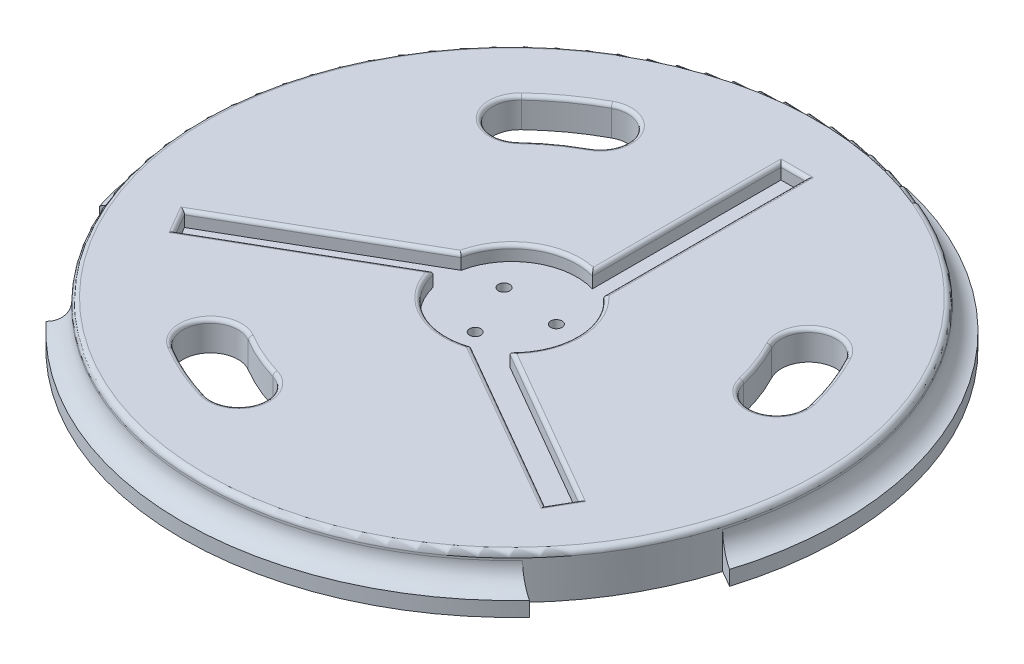
SolidWorks part; units mm, degrees
ref_plane "Alzado" through (0, 0, 0) normal (0, 0, 1) x (1, 0, 0)
ref_plane "Planta" through (0, 0, 0) normal (0, 1, 0) x (1, 0, 0)
ref_plane "Vista lateral" through (0, 0, 0) normal (1, 0, 0) x (0, 0, -1)
sketch "Croquis1" plane through (0, 0, 0) normal (0, 1, 0) x (1, 0, 0)
  line L9 (-64.9347, -24.2163) -> (-2.1479, 12.0337)
  line L10 (-2.1479, 12.0337) -> (1.0271, 6.5345)
  line L11 (1.0271, 6.5345) -> (-61.7597, -29.7155)
  line L12 (-61.7597, -29.7155) -> (-64.9347, -24.2163)
  line L13 (53.3875, -44.1301) -> (-9.3993, -7.8801)
  line L14 (-9.3993, -7.8801) -> (-6.2243, -2.3808)
  line L15 (-6.2243, -2.3808) -> (56.5625, -38.6308)
  line L16 (56.5625, -38.6308) -> (53.3875, -44.1301)
  line L17 (11.524, 68.3) -> (11.524, -4.2)
  line L18 (11.524, -4.2) -> (5.174, -4.2)
  line L19 (5.174, -4.2) -> (5.174, 68.3)
  line L20 (5.174, 68.3) -> (11.524, 68.3)
  line L21 (-7.4511, 5.3057) -> (-0.5604, 9.2841)
  line L22 (-7.4511, 5.3057) -> (-9.0386, 8.0553)
  line L23 (-0.8836, -9.1304) -> (-7.8118, -5.1304)
  line L24 (-0.8836, -9.1304) -> (-2.4711, -11.8801)
  line L25 (8.349, 3.8) -> (8.349, -4.2)
  line L26 (8.349, 3.8) -> (11.524, 3.8)
  arc A0 (11.8909, -12.8396) -> (11.524, 13.17) centre (0, 0) ccw
  arc A1 (-17.0583, -3.9072) -> (5.6435, -16.565) centre (0, 0) ccw
  arc A2 (5.174, 16.7177) -> (-17.1748, 3.3579) centre (0, 0) ccw
  circle A3 centre (-0.8836, -9.1304) radius 1.625
  circle A4 centre (-7.4511, 5.3057) radius 1.625
  circle A5 centre (8.349, 3.8) radius 1.625
sketch "Croquis2" plane through (0, 0, 0) normal (0, 1, 0) x (1, 0, 0)
  line L0 (-64.9347, -24.2163) -> (-2.1479, 12.0337) construction
  line L1 (1.0271, 6.5345) -> (-61.7597, -29.7155) construction
  line L2 (-61.7597, -29.7155) -> (-64.9347, -24.2163) construction
  line L3 (53.3875, -44.1301) -> (-9.3993, -7.8801) construction
  line L4 (-6.2243, -2.3808) -> (56.5625, -38.6308) construction
  line L5 (5.174, -4.2) -> (5.174, 68.3) construction
  line L6 (11.524, 68.3) -> (11.524, -4.2) construction
  line L7 (5.174, 68.3) -> (11.524, 68.3) construction
  line L8 (5.174, 68.3) -> (11.524, 68.3) construction
  line L9 (11.524, 68.3) -> (11.524, 13.17) construction
  line L10 (5.174, 16.7177) -> (5.174, 68.3) construction
  line L11 (11.8909, -12.8396) -> (56.5625, -38.6308) construction
  line L12 (53.3875, -44.1301) -> (5.6435, -16.565) construction
  line L13 (-61.7597, -29.7155) -> (-64.9347, -24.2163) construction
  line L14 (-17.0583, -3.9072) -> (-61.7597, -29.7155) construction
  line L15 (-64.9347, -24.2163) -> (-17.1748, 3.3579) construction
  line L16 (56.5625, -38.6308) -> (53.3875, -44.1301) construction
  line L17 (-65.2762, -24.1248) -> (-17.3979, 3.5178)
  line L18 (-61.8512, -30.057) -> (-65.2762, -24.1248)
  line L19 (-17.2235, -4.2912) -> (-61.8512, -30.057)
  line L20 (53.4791, -44.4716) -> (5.6164, -16.838)
  line L21 (56.9041, -38.5393) -> (53.4791, -44.4716)
  line L22 (12.3066, -12.791) -> (56.9041, -38.5393)
  line L23 (11.774, 68.55) -> (11.774, 13.2829)
  line L24 (4.924, 68.55) -> (11.774, 68.55)
  line L25 (4.924, 17.0534) -> (4.924, 68.55)
  circle A0 centre (0, 0) radius 85
  arc A1 (-17.0583, -3.9072) -> (5.6435, -16.565) centre (0, 0) ccw construction
  arc A2 (11.8909, -12.8396) -> (11.524, 13.17) centre (0, 0) ccw construction
  arc A3 (5.174, 16.7177) -> (-17.1748, 3.3579) centre (0, 0) ccw construction
  arc A4 (5.174, 16.7177) -> (-17.1748, 3.3579) centre (0, 0) ccw construction
  arc A5 (11.8909, -12.8396) -> (11.524, 13.17) centre (0, 0) ccw construction
  arc A6 (-17.0583, -3.9072) -> (5.6435, -16.565) centre (0, 0) ccw construction
  arc A7 (4.924, 17.0534) -> (-17.3979, 3.5178) centre (0, 0) ccw
  arc A8 (-17.2235, -4.2912) -> (5.6164, -16.838) centre (0, 0) ccw
  arc A9 (12.3066, -12.791) -> (11.774, 13.2829) centre (0, 0) ccw
  dimension "D1" = 170
  dimension "D2" = 0.25
extrude "Saliente-Extruir1" add sketch "Croquis2" along normal blind 4
sketch "Croquis3" plane through (0, 0, 0) normal (0, 1, 0) x (1, 0, 0)
  circle A0 centre (0, 0) radius 85
  dimension "D1" = 170
extrude "Saliente-Extruir2" add sketch "Croquis3" against normal blind 4
sketch "Croquis4" plane through (0, 0, 0) normal (0, 1, 0) x (1, 0, 0)
  circle A0 centre (-0.8836, -9.1304) radius 1.625 construction
  circle A1 centre (8.349, 3.8) radius 1.625 construction
  circle A2 centre (-7.4511, 5.3057) radius 1.625 construction
  circle A3 centre (-0.8836, -9.1304) radius 1.625
  circle A4 centre (8.349, 3.8) radius 1.625
  circle A5 centre (-7.4511, 5.3057) radius 1.625
  circle A6 centre (-7.4511, 5.3057) radius 1.625
  circle A7 centre (8.349, 3.8) radius 1.55
  circle A8 centre (-0.8836, -9.1304) radius 1.55
  circle A9 centre (-7.4511, 5.3057) radius 1.55
  dimension "D1" = 3.1
  dimension "D2" = 3.1
  dimension "D3" = 3.1
extrude "Cortar-Extruir2" cut sketch "Croquis4" against normal blind 4 contours A9 | A7 | A8 region at (8.349, 0, -3.8) region at (-0.8836, 0, 9.1304) region at (-7.4511, 0, -5.3057)
sketch "Croquis5" plane through (0, -4, 0) normal (0, -1, 0) x (1, 0, 0)
  circle A0 centre (0, 0) radius 90
  circle A1 centre (0, 0) radius 85
  circle A2 centre (0, 0) radius 85 construction
  circle A3 centre (0, 0) radius 80
  dimension "D4" = 180
  dimension "D1" = 0
  dimension "D2" = 5
  dimension "D3" = 5
extrude "Saliente-Extruir3" add sketch "Croquis5" along normal blind 4
fillet "Redondeo1" radius 20 1 edges at (0, -4, -80)
sketch "Croquis6" plane through (0, 4, 0) normal (0, 1, 0) x (1, 0, 0)
  line L0 (0, 0) -> (-17.0749, -57.5191) construction
  line L1 (0, 0) -> (-41.2755, 43.5469) construction
  line L2 (0, 0) -> (58.3505, 13.9722) construction
  circle A0 centre (0, 0) radius 60 construction
  circle A1 centre (0, 0) radius 85
  circle A2 centre (0, 0) radius 85 construction
  arc A3 (58.3505, 13.9722) -> (53.0797, 27.974) centre (0, 0) ccw construction
  arc A4 (65.6443, 15.7188) -> (59.7147, 31.4708) centre (0, 0) ccw
  arc A5 (51.0567, 12.2257) -> (46.4447, 24.4773) centre (0, 0) ccw
  arc A6 (51.0567, 12.2257) -> (65.6443, 15.7188) centre (58.3505, 13.9722) ccw
  arc A7 (59.7147, 31.4708) -> (46.4447, 24.4773) centre (53.0797, 27.974) ccw
  arc A8 (-17.0749, -57.5191) -> (-30.7746, -51.5066) centre (0, 0) cw construction
  arc A9 (-34.6214, -57.9449) -> (-19.2093, -64.709) centre (0, 0) ccw
  arc A10 (-26.9277, -45.0682) -> (-14.9406, -50.3292) centre (0, 0) ccw
  arc A11 (-26.9277, -45.0682) -> (-34.6214, -57.9449) centre (-30.7746, -51.5066) ccw
  arc A12 (-19.2093, -64.709) -> (-14.9406, -50.3292) centre (-17.0749, -57.5191) ccw
  arc A13 (-41.2755, 43.5469) -> (-28.5983, 52.7459) centre (0, 0) cw construction
  arc A14 (-32.1731, 59.3392) -> (-46.435, 48.9902) centre (0, 0) ccw
  arc A15 (-25.0236, 46.1527) -> (-36.1161, 38.1035) centre (0, 0) ccw
  arc A16 (-25.0236, 46.1527) -> (-32.1731, 59.3392) centre (-28.5983, 52.7459) ccw
  arc A17 (-46.435, 48.9902) -> (-36.1161, 38.1035) centre (-41.2755, 43.5469) ccw
  point P8 (56.1532, 21.138)
  point P16 (-24.1129, -54.9415)
  point P21 (-35.2384, 48.5619)
  dimension "D2" = 120
  dimension "D3" = 120
  dimension "D4" = 120
  dimension "D1" = 0
extrude "Cortar-Extruir3" cut sketch "Croquis6" against normal blind 14
sketch "Croquis7" plane through (0, 0, 0) normal (0, 1, 0) x (1, 0, 0)
  line L0 (0, 0) -> (0, 90) construction
  line L1 (0, 0) -> (-77.9423, -45) construction
  line L2 (0, 0) -> (77.9423, -45) construction
  line L3 (-85.9934, -26.5543) -> (-81.5454, -23.9863)
  line L4 (-65.9934, -61.1953) -> (-61.5454, -58.6273)
  line L5 (85.9934, -26.5543) -> (81.5454, -23.9863)
  line L6 (65.9934, -61.1953) -> (61.5454, -58.6273)
  line L7 (-20, 87.7496) -> (-20, 82.6136)
  line L8 (20, 82.6136) -> (20, 87.7496)
  circle A1 centre (0, 0) radius 90
  circle A2 centre (0, 0) radius 90
  circle A3 centre (0, 0) radius 85
  circle A4 centre (0, 0) radius 85
  dimension "D3" = 120
  dimension "D4" = 120
  dimension "D5" = 20
  dimension "D6" = 20
  dimension "D7" = 20
  dimension "D8" = 20
  dimension "D9" = 20
  dimension "D10" = 20
  dimension "D1" = 0
  dimension "D2" = 0
extrude "Cortar-Extruir4" cut sketch "Croquis7" against normal blind 14 contours A4 L8 A2 L7 | A4 L3 A2 L4 | A4 L6 A2 L5 region at (-75.1068, 0, 43.3629) region at (0, 0, -86.7258) region at (75.1068, 0, 43.3629)
fillet "Redondeo2" radius 6 3 edges at (0, -4, 85) (-73.6122, -4, -42.5) (73.6122, -4, -42.5)
fillet "Redondeo3" radius 1.5 1 edges at (0, 4, 85)
fillet "Redondeo5" radius 1 24 edges at (-63.5637, 4, 27.0909) (-39.5373, 4, 17.1741) (-8.5462, 4, 15.5572) (29.5477, 4, 30.6548) (55.1916, 4, 41.5054) (34.6054, 4, 25.6651) (17.7463, 4, -0.3625) (11.774, 4, -40.9165) (8.349, 4, -68.55) (4.924, 4, -42.8017) (-9.2034, 4, -15.1776) (-41.3371, 4, 10.3035) (-39.6432, 4, -54.6321) (-46.7189, 4, -38.3874) (-30.8336, 4, -42.4916) (-22.0051, 4, -56.3207) (-27.127, 4, 61.8092) (-9.885, 4, 59.6535) (-21.0988, 4, 48.0738) (-37.2129, 4, 47.6597) (63.1724, 4, -23.7803) (49.583, 4, -34.609) (49.1341, 4, -18.4958) (60.097, 4, -6.6784)
